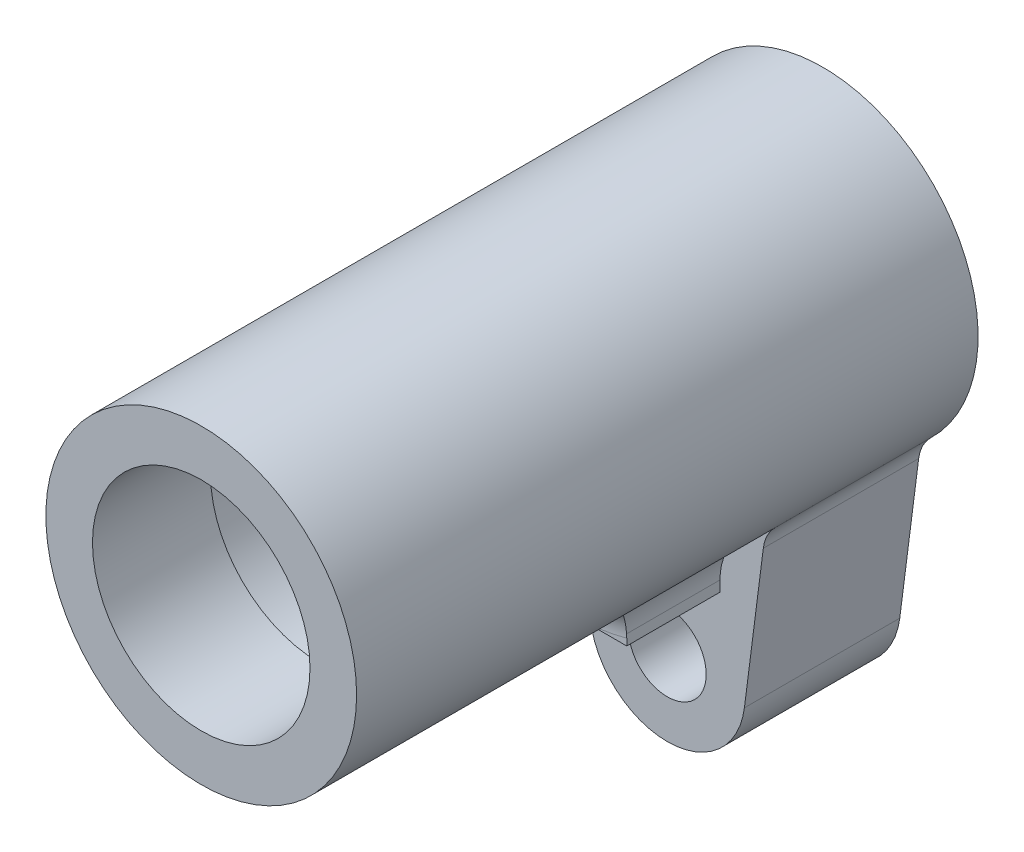
SolidWorks part; units mm, degrees
ref_plane "Front Plane" through (0, 0, 0) normal (0, 0, 1) x (1, 0, 0)
ref_plane "Top Plane" through (0, 0, 0) normal (0, 1, 0) x (1, 0, 0)
ref_plane "Right Plane" through (0, 0, 0) normal (1, 0, 0) x (0, 0, -1)
sketch "Sketch1" plane through (0, 0, 0) normal (0, 0, 1) x (1, 0, 0)
  circle A0 centre (0, 0) radius 35
  circle A1 centre (0, 0) radius 50
  dimension "D1" = 100
  dimension "D2" = 70
extrude "Boss-Extrude1" add sketch "Sketch1" along normal blind 162
sketch "Sketch4" plane through (0, 0, 162) normal (0, 0, 1) x (1, 0, 0)
  circle A0 centre (0, 0) radius 37.5
  dimension "D1" = 75
extrude "Cut-Extrude1" cut sketch "Sketch4" against normal blind 87
sketch "Sketch5" plane through (0, 0, 162) normal (0, 0, 1) x (1, 0, 0)
  circle A0 centre (0, 0) radius 50
  circle A1 centre (0, 0) radius 35
  dimension "D1" = 70
extrude "Boss-Extrude2" add sketch "Sketch5" along normal blind 38
sketch "Sketch7" plane through (0, 0, 0) normal (0, 0, -1) x (-1, 0, 0)
  line L0 (0, 0) -> (0, -139.1455) construction
  line L1 (-31.5, -38.8298) -> (-24.7975, -91.1751)
  line L2 (24.7917, -91.2202) -> (31.5, -38.8298)
  line L3 (31.5, -38.8298) -> (-31.5, -38.8298)
  circle A0 centre (0, 0) radius 50 construction
  arc A1 (-24.7975, -91.1751) -> (24.7917, -91.2202) centre (0, -88) ccw
  circle A2 centre (0, -88) radius 12.5
  dimension "D1" = 25
  dimension "D4" = 25
  dimension "D2" = 63
  dimension "D3" = 88
extrude "Boss-Extrude3" add sketch "Sketch7" against normal blind 50
fillet "Fillet2" radius 13 1 edges at (-31.5, -38.8298, 25)
fillet "Fillet3" radius 13 1 edges at (31.5, -38.8298, 25)
sketch "Sketch8" plane through (0, 0, 50) normal (0, 0, 1) x (1, 0, 0)
  line L0 (-16.9391, -47.0432) -> (-16.9391, -62.8661)
  line L1 (-16.9391, -62.8661) -> (16.9391, -62.8661)
  line L2 (16.9391, -62.8661) -> (16.9391, -47.0432)
  line L3 (16.9391, -47.0432) -> (-16.9391, -47.0432)
  line L4 (-16.9391, -47.0432) -> (16.9391, -62.8661) construction
  line L5 (16.9391, -47.0432) -> (-16.9391, -62.8661) construction
  line L6 (0, 0) -> (0, -88.6152) construction
  circle A0 centre (0, 0) radius 50 construction
extrude "Boss-Extrude4" add sketch "Sketch8" along normal blind 30
fillet "Fillet4" radius 13 1 edges at (0, -50, 80)
fillet "Fillet5" radius 20 1 edges at (16.9391, -47.0432, 71.5)
fillet "Fillet6" radius 20 1 edges at (-16.9391, -47.0432, 71.5)
sketch "Sketch10" plane through (0, -62.8661, 0) normal (0, -1, 0) x (1, 0, 0)
  line L0 (-4.105, 80) -> (4.105, 80) construction
  line L1 (0, 80) -> (0, 40.2701) construction
  line L2 (-24.7917, 0) -> (24.7975, 0) construction
  circle A0 centre (0, 60) radius 8
  dimension "D1" = 16
  dimension "D2" = 20
  dimension "D3" = 60
extrude "Cut-Extrude2" cut sketch "Sketch10" against normal blind 57
